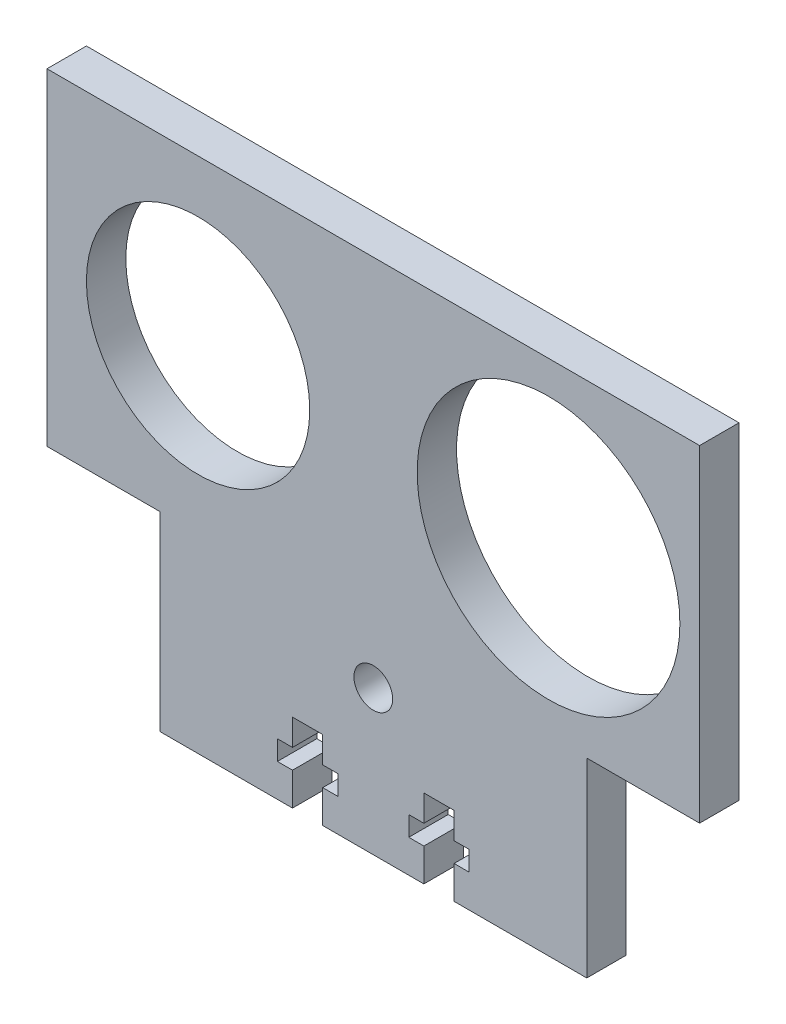
SolidWorks part; units mm, degrees
material "ABS"
ref_plane "Front Plane" through (0, 0, 0) normal (0, 0, 1) x (1, 0, 0)
ref_plane "Top Plane" through (0, 0, 0) normal (0, 1, 0) x (1, 0, 0)
ref_plane "Right Plane" through (0, 0, 0) normal (1, 0, 0) x (0, 0, -1)
sketch "Sketch1" plane through (0, 0, 0) normal (0, 0, 1) x (1, 0, 0)
  line L0 (0, 0) -> (-26.6757, 31.7908) construction
  line L1 (0, 0) -> (0, 56.7908) construction
  line L2 (-32.5, 7) -> (-32.5, -22)
  line L3 (-32.5, -22) -> (32.5, -22)
  line L4 (32.5, 7) -> (49.6757, 7)
  line L5 (0, 0) -> (0, -22) construction
  line L6 (49.6757, 7) -> (49.6757, 56.7908)
  line L7 (0, 0) -> (26.6757, 31.7908) construction
  line L10 (-32.5, 7) -> (-49.6757, 7)
  line L11 (-49.6757, 7) -> (-49.6757, 56.7908)
  line L12 (-49.6757, 56.7908) -> (49.6757, 56.7908)
  line L13 (32.5, 7) -> (32.5, -22)
  circle A0 centre (0, 0) radius 2.95
  circle A1 centre (-26.6757, 31.7908) radius 17
  circle A2 centre (26.6757, 31.7908) radius 20
  point P16 (0, 56.7908)
  dimension "D1" = 5.9
  dimension "D9" = 34
  dimension "D10" = 40
  dimension "D2" = 41.5
  dimension "D4" = 40
  dimension "D5" = 22
  dimension "D6" = 65
  dimension "D7" = 29
  dimension "D8" = 23
  dimension "D3" = 25
  dimension "D11" = 40
extrude "Boss-Extrude1" add sketch "Sketch1" along normal blind 6
sketch "Sketch3" plane through (0, 0, 6) normal (0, 0, 1) x (1, 0, 0)
  line L0 (-32.5, -22) -> (32.5, -22) construction
  line L1 (-12.3, -22) -> (-7.7, -22)
  line L2 (-12.3, -22) -> (-12.3, -17)
  line L3 (-12.3, -10) -> (-7.7, -10)
  line L4 (-7.7, -22) -> (-7.7, -17)
  line L5 (0, 0) -> (0, -22) construction
  line L6 (-7.7, -14) -> (-5.4, -14)
  line L7 (-14.6, -14) -> (-12.3, -14)
  line L8 (-14.6, -14) -> (-14.6, -17)
  line L9 (-14.6, -17) -> (-12.3, -17)
  line L10 (-5.4, -14) -> (-5.4, -17)
  line L11 (-12.3, -14) -> (-12.3, -10)
  line L12 (-7.7, -17) -> (-5.4, -17)
  line L13 (-7.7, -14) -> (-7.7, -10)
  line L14 (7.7, -14) -> (7.7, -10)
  line L15 (7.7, -17) -> (5.4, -17)
  line L16 (12.3, -14) -> (12.3, -10)
  line L17 (5.4, -14) -> (5.4, -17)
  line L18 (14.6, -17) -> (12.3, -17)
  line L19 (14.6, -14) -> (14.6, -17)
  line L20 (14.6, -14) -> (12.3, -14)
  line L21 (7.7, -14) -> (5.4, -14)
  line L22 (7.7, -22) -> (7.7, -17)
  line L23 (12.3, -10) -> (7.7, -10)
  line L24 (12.3, -22) -> (12.3, -17)
  line L25 (12.3, -22) -> (7.7, -22)
  point P6 (-10, -10)
  point P18 (-13.45, -17)
  dimension "D1" = 4.6
  dimension "D2" = 10
  dimension "D3" = 12
  dimension "D4" = 9.2
  dimension "D5" = 3
  dimension "D6" = 5
extrude "Cut-Extrude2" cut sketch "Sketch3" against normal through all
equation "\"smallPulleyTeeth\"= 15"
equation "\"largePulleyTeeth\"= 30"
equation "\"eighthThick\"= 2.9mm"
equation "\"sixteenthThick\" = 1.7mm"
equation "\"quarterThick\"=6.0mm"
equation "\"OD\" = 145mm"
equation "\"puckAngle\" = 60.5deg"
equation "\"puckDiam\" = 76.5mm"
equation "\"axlePress\" = 5.9mm"
equation "\"D1@Sketch1\"=\"axlePress\""
equation "\"D1@Boss-Extrude1\"=\"quarterThick\""
equation "\"press\" = 0.2mm"
equation "\"wheelClear\" = 0.3mm"
equation "\"10-32clear\" = 4.8mm"
equation "\"D1@Sketch3\"=\"10-32clear\" - \"press\""
equation "\"6-32clear\" = 3.3mm"
equation "\"8-32clear\" = 4.0mm"
equation "\"wheelHeight\" = 22mm"
equation "\"D5@Sketch1\"=\"wheelHeight\""
equation "\"D7@Sketch1\"=\"eighthThick\"*10"
equation "\"4-40clear\" = 3.0mm"
equation "\"wheelWell\" = 65mm"
equation "\"D6@Sketch1\"=\"wheelWell\""
